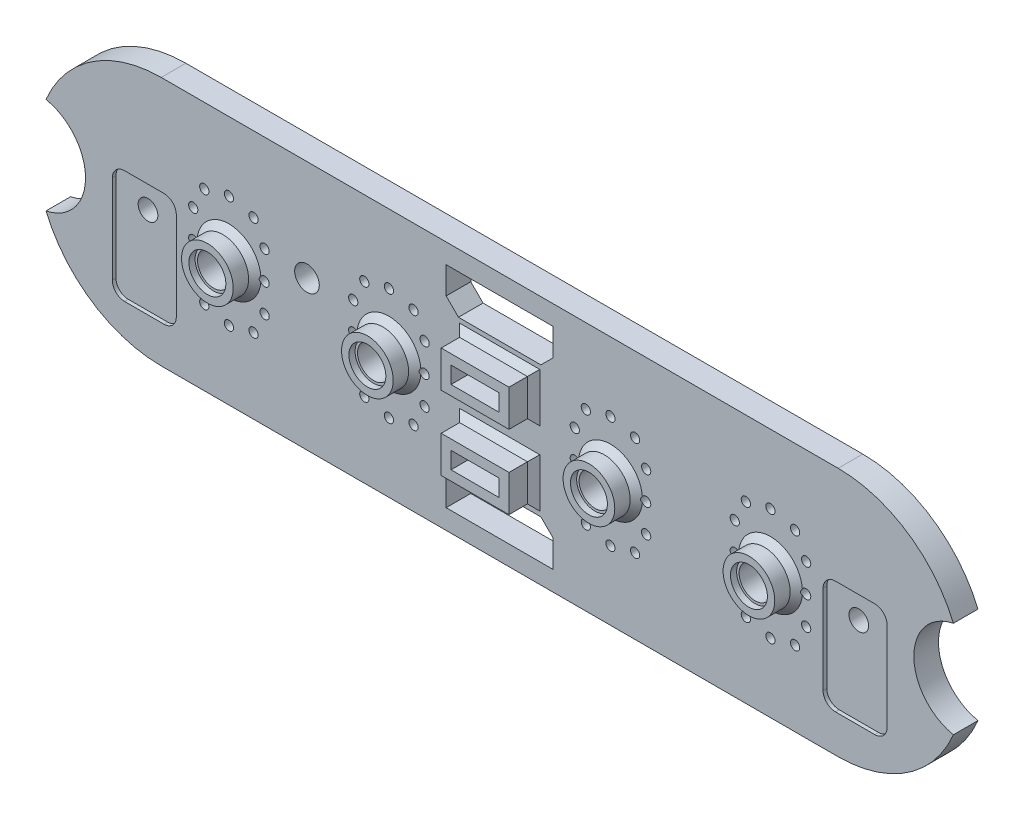
SolidWorks part; units mm, degrees
ref_plane "Plan de face" through (0, 0, 0) normal (0, 0, 1) x (1, 0, 0)
ref_plane "Plan de dessus" through (0, 0, 0) normal (0, 1, 0) x (1, 0, 0)
ref_plane "Plan de droite" through (0, 0, 0) normal (1, 0, 0) x (0, 0, -1)
sketch "Esquisse1" plane through (0, 0, 0) normal (0, 0, 1) x (1, 0, 0)
  line L0 (-55, 0) -> (55, 0) construction
  line L1 (-55, 22.5) -> (55, 22.5) construction
  line L2 (-55, -22.5) -> (55, -22.5) construction
  line L3 (-55, 20.3) -> (55, 20.3)
  line L4 (-55, -20.3) -> (55, -20.3)
  arc A0 (-55, 22.5) -> (-55, -22.5) centre (-55, 0) ccw construction
  arc A1 (55, -22.5) -> (55, 22.5) centre (55, 0) ccw construction
  arc A2 (55, -20.3) -> (55, 20.3) centre (55, 0) ccw
  arc A3 (-55, 20.3) -> (-55, -20.3) centre (-55, 0) ccw
  point P2 (0, 0)
  dimension "D1" = 110
  dimension "D2" = 45
  dimension "D3" = 2.2
extrude "Boss.-Extru.1" add sketch "Esquisse1" along normal blind 4
sketch "Esquisse5" plane through (0, 0, 4) normal (0, 0, 1) x (1, 0, 0)
  line L0 (0, -55) -> (0, 55) construction
  arc A0 (-73.7236, 7.8432) -> (-73.7236, -7.8432) centre (-75.3, 0) cw
  arc A1 (-55, 20.3) -> (-55, -20.3) centre (-55, 0) ccw construction
  arc A2 (-73.7236, 7.8432) -> (-73.7236, -7.8432) centre (-55, 0) ccw
  arc A3 (73.7236, 7.8432) -> (73.7236, -7.8432) centre (75.3, 0) ccw
  arc A4 (73.7236, 7.8432) -> (73.7236, -7.8432) centre (55, 0) cw
  dimension "D1" = 8
extrude "Enlèv. mat.-Extru.2" cut sketch "Esquisse5" against normal through all
sketch "Esquisse6" plane through (0, 0, 4) normal (0, 0, 1) x (1, 0, 0)
  line L1 (-57.75, 0) -> (57.75, 0) construction
  circle A0 centre (-57.75, 0) radius 1.6
  circle A1 centre (57.75, 0) radius 1.6
  point P6 (0, 0)
  dimension "D1" = 3.2
  dimension "D2" = 115.5
extrude "Enlèv. mat.-Extru.3" cut sketch "Esquisse6" against normal through all
sketch "Esquisse7" plane through (0, 0, 4) normal (0, 0, 1) x (1, 0, 0)
  line L1 (-62.75, 4) -> (-52.75, 4) construction
  line L2 (-62.75, 4) -> (-62.75, -14) construction
  line L3 (-62.75, -14) -> (-52.75, -14) construction
  line L4 (-52.75, 4) -> (-52.75, -14) construction
  line L5 (-60.95, 4.2) -> (-54.55, 4.2)
  line L6 (-52.55, 2.2) -> (-52.55, -12.2)
  line L7 (-60.95, -14.2) -> (-54.55, -14.2)
  line L8 (-62.95, 2.2) -> (-62.95, -12.2)
  line L9 (-62.95, 4.2) -> (-62.95, -14.2) construction
  line L10 (-62.95, -14.2) -> (-52.55, -14.2) construction
  line L11 (-52.55, 4.2) -> (-52.55, -14.2) construction
  line L12 (-62.95, 4.2) -> (-52.55, 4.2) construction
  line L13 (0, -55) -> (0, 55) construction
  line L14 (60.95, 4.2) -> (54.55, 4.2)
  line L15 (52.55, 2.2) -> (52.55, -12.2)
  line L16 (60.95, -14.2) -> (54.55, -14.2)
  line L17 (62.95, 2.2) -> (62.95, -12.2)
  arc A1 (-62.95, -12.2) -> (-60.95, -14.2) centre (-60.95, -12.2) ccw
  arc A2 (-52.55, -12.2) -> (-54.55, -14.2) centre (-54.55, -12.2) cw
  arc A3 (-54.55, 4.2) -> (-52.55, 2.2) centre (-54.55, 2.2) cw
  arc A4 (-60.95, 4.2) -> (-62.95, 2.2) centre (-60.95, 2.2) ccw
  arc A5 (60.95, 4.2) -> (62.95, 2.2) centre (60.95, 2.2) cw
  arc A6 (54.55, 4.2) -> (52.55, 2.2) centre (54.55, 2.2) ccw
  arc A7 (52.55, -12.2) -> (54.55, -14.2) centre (54.55, -12.2) ccw
  arc A8 (62.95, -12.2) -> (60.95, -14.2) centre (60.95, -12.2) cw
  circle A9 centre (-57.75, 0) radius 1.6 construction
  dimension "D5" = 2
  dimension "D1" = 10
  dimension "D2" = 18
  dimension "D3" = 4
  dimension "D4" = 0.2
  dimension "D6" = 5
extrude "Enlèv. mat.-Extru.4" cut sketch "Esquisse7" against normal blind 0.6
sketch "Esquisse2" plane through (0, 0, 4) normal (0, 0, 1) x (1, 0, 0)
  line L0 (-18, 0) -> (-12.2, 0) construction
  line L1 (-18, 0) -> (-18, 9.1) construction
  line L2 (0, -55) -> (0, 55) construction
  line L3 (0, -6) -> (0, 6) construction
  line L4 (-18, 0) -> (-13.9991, 8.0953) construction
  line L5 (-13.9991, 8.0953) -> (-18, 0) construction
  line L6 (-18, 0) -> (-12.2007, 4.5965) construction
  line L7 (-3.91, 7.37) -> (3.91, 7.37)
  line L8 (-12.2007, -4.5965) -> (-18, 0) construction
  line L9 (-18, 0) -> (-13.9991, -8.0953) construction
  line L10 (-13.9991, -8.0953) -> (-18, 0) construction
  line L11 (-3.91, 7.37) -> (-3.91, 4.63)
  line L12 (-3.91, 4.63) -> (3.91, 4.63)
  line L13 (-18, -9.1) -> (-18, 0) construction
  line L14 (3.91, 7.37) -> (3.91, 4.63)
  line L15 (-3.91, 7.37) -> (3.91, 4.63) construction
  line L16 (-22.0009, -8.0953) -> (-18, 0) construction
  line L17 (-18, 0) -> (-23.7993, -4.5965) construction
  line L18 (-3.91, 4.63) -> (3.91, 7.37) construction
  line L19 (-23.8, 0) -> (-18, 0) construction
  line L20 (-18, 0) -> (-23.7993, 4.5965) construction
  line L21 (-3.91, -4.63) -> (3.91, -4.63)
  line L22 (-22.0009, 8.0953) -> (-18, 0) construction
  line L23 (-3.91, -4.63) -> (-3.91, -7.37)
  line L24 (-3.91, -7.37) -> (3.91, -7.37)
  line L25 (3.91, -4.63) -> (3.91, -7.37)
  line L26 (-3.91, -4.63) -> (3.91, -7.37) construction
  line L27 (-3.91, -7.37) -> (3.91, -4.63) construction
  circle A0 centre (-18, 9.1) radius 0.75
  circle A1 centre (-13.9991, 8.0953) radius 0.75
  circle A2 centre (-12.2007, 4.5965) radius 0.75
  circle A3 centre (-12.2, 0) radius 0.75
  circle A4 centre (-12.2007, -4.5965) radius 0.75
  circle A5 centre (-13.9991, -8.0953) radius 0.75
  circle A6 centre (-18, -9.1) radius 0.75
  circle A7 centre (-22.0009, -8.0953) radius 0.75
  circle A8 centre (-23.7993, -4.5965) radius 0.75
  circle A9 centre (-23.8, 0) radius 0.75
  circle A10 centre (-23.7993, 4.5965) radius 0.75
  circle A11 centre (-22.0009, 8.0953) radius 0.75
  circle A12 centre (-18, 0) radius 2.6
  circle A13 centre (-48.0009, 8.0953) radius 0.75
  circle A14 centre (-49.7993, 4.5965) radius 0.75
  circle A15 centre (-49.8, 0) radius 0.75
  circle A16 centre (-49.7993, -4.5965) radius 0.75
  circle A17 centre (-44, 0) radius 2.6
  circle A18 centre (-48.0009, -8.0953) radius 0.75
  circle A19 centre (-44, -9.1) radius 0.75
  circle A20 centre (-39.9991, -8.0953) radius 0.75
  circle A21 centre (-38.2007, -4.5965) radius 0.75
  circle A22 centre (-38.2, 0) radius 0.75
  circle A23 centre (-38.2007, 4.5965) radius 0.75
  circle A24 centre (-39.9991, 8.0953) radius 0.75
  circle A25 centre (-44, 9.1) radius 0.75
  circle A26 centre (44, 9.1) radius 0.75
  circle A27 centre (39.9991, 8.0953) radius 0.75
  circle A28 centre (38.2007, 4.5965) radius 0.75
  circle A29 centre (38.2, 0) radius 0.75
  circle A30 centre (38.2007, -4.5965) radius 0.75
  circle A31 centre (39.9991, -8.0953) radius 0.75
  circle A32 centre (44, -9.1) radius 0.75
  circle A33 centre (48.0009, -8.0953) radius 0.75
  circle A34 centre (44, 0) radius 2.6
  circle A35 centre (49.7993, -4.5965) radius 0.75
  circle A36 centre (49.8, 0) radius 0.75
  circle A37 centre (49.7993, 4.5965) radius 0.75
  circle A38 centre (48.0009, 8.0953) radius 0.75
  circle A39 centre (18, 9.1) radius 0.75
  circle A40 centre (13.9991, 8.0953) radius 0.75
  circle A41 centre (12.2007, 4.5965) radius 0.75
  circle A42 centre (12.2, 0) radius 0.75
  circle A43 centre (12.2007, -4.5965) radius 0.75
  circle A44 centre (13.9991, -8.0953) radius 0.75
  circle A45 centre (18, -9.1) radius 0.75
  circle A46 centre (22.0009, -8.0953) radius 0.75
  circle A47 centre (18, 0) radius 2.6
  circle A48 centre (23.7993, -4.5965) radius 0.75
  circle A49 centre (23.8, 0) radius 0.75
  circle A50 centre (23.7993, 4.5965) radius 0.75
  circle A51 centre (22.0009, 8.0953) radius 0.75
  point P2 (0, 6)
  point P112 (0, -6)
  point P120 (0, 0)
  dimension "D10" = 1.5
  dimension "D11" = 5.2
  dimension "D1" = 5.8
  dimension "D2" = 7.4
  dimension "D3" = 9.03
  dimension "D4" = 18
  dimension "D5" = 9.1
  dimension "D6" = 38.4
  dimension "D7" = 63.7
  dimension "D8" = 38.4
  dimension "D9" = 63.7
  dimension "D13" = 12
  dimension "D14" = 2.74
  dimension "D15" = 7.82
  dimension "D12" = 2
extrude "Enlèv. mat.-Extru.1" cut sketch "Esquisse2" against normal through all
sketch "Esquisse3" plane through (0, 0, 4) normal (0, 0, 1) x (1, 0, 0)
  circle A1 centre (-18, 0) radius 2.6 construction
  circle A2 centre (-18, 0) radius 2.6
  circle A4 centre (44, 0) radius 2.6 construction
  circle A5 centre (18, 0) radius 2.6 construction
  circle A6 centre (-44, 0) radius 2.6 construction
  circle A7 centre (44, 0) radius 2.6
  circle A8 centre (18, 0) radius 2.6
  circle A9 centre (-44, 0) radius 2.6
  circle A10 centre (-44, 0) radius 4.2
  circle A11 centre (-18, 0) radius 4.2
  circle A12 centre (18, 0) radius 4.2
  circle A13 centre (44, 0) radius 4.2
  dimension "D1" = 1.6
extrude "Boss.-Extru.2" add sketch "Esquisse3" along normal blind 3.5
sketch "Esquisse9" plane through (0, 0, 7.5) normal (0, 0, 1) x (1, 0, 0)
  circle A0 centre (-44, 0) radius 3
  circle A1 centre (-18, 0) radius 3
  circle A2 centre (18, 0) radius 3
  circle A3 centre (44, 0) radius 3
  dimension "D1" = 6
extrude "Enlèv. mat.-Extru.6" cut sketch "Esquisse9" against normal blind 1
sketch "Esquisse4" plane through (0, 0, 4) normal (0, 0, 1) x (1, 0, 0)
  line L2 (5.51, -8.97) -> (5.51, -3.03)
  line L3 (5.51, -3.03) -> (-5.51, -3.03)
  line L4 (-5.51, -3.03) -> (-5.51, -8.97)
  line L5 (-5.51, -8.97) -> (5.51, -8.97)
  line L6 (3.91, -7.37) -> (3.91, -4.63)
  line L7 (-3.91, -7.37) -> (3.91, -7.37)
  line L8 (-3.91, -4.63) -> (-3.91, -7.37)
  line L9 (3.91, -4.63) -> (-3.91, -4.63)
  line L10 (3.91, -7.37) -> (3.91, -4.63)
  line L11 (-3.91, -7.37) -> (3.91, -7.37)
  line L12 (-3.91, -4.63) -> (-3.91, -7.37)
  line L13 (3.91, -4.63) -> (-3.91, -4.63)
  line L14 (3.91, 4.63) -> (3.91, 7.37)
  line L15 (-3.91, 4.63) -> (3.91, 4.63)
  line L16 (-3.91, 7.37) -> (-3.91, 4.63)
  line L17 (3.91, 7.37) -> (-3.91, 7.37)
  line L18 (3.91, 4.63) -> (3.91, 7.37)
  line L19 (-3.91, 4.63) -> (3.91, 4.63)
  line L20 (-3.91, 7.37) -> (-3.91, 4.63)
  line L21 (3.91, 7.37) -> (-3.91, 7.37)
  line L22 (5.51, 3.03) -> (5.51, 8.97)
  line L23 (5.51, 8.97) -> (-5.51, 8.97)
  line L24 (-5.51, 8.97) -> (-5.51, 3.03)
  line L25 (-5.51, 3.03) -> (5.51, 3.03)
  dimension "D1" = 0
  dimension "D2" = 0
  dimension "D3" = 1.6
extrude "Boss.-Extru.3" add sketch "Esquisse4" along normal offset from surface (4 mm away) 8 up to face at (-47.2509, 8.0953, 0)
chamfer "Chanfrein1" distance 1 angle 45 12 edges at (48.2, 0, 4) (22.2, 0, 4) (-13.8, 0, 4) (-39.8, 0, 4) (0, -3.03, 4) (5.51, -6, 4) (0, -8.97, 4) (-5.51, -6, 4) (0, 3.03, 4) (-5.51, 6, 4) (5.51, 6, 4) (0, 8.97, 4)
fillet "Congé1" radius 2 4 edges at (-41.4, 0, 0) (-15.4, 0, 0) (15.4, 0, 0) (41.4, 0, 0)
sketch "Esquisse8" plane through (0, 0, 4) normal (0, 0, 1) x (1, 0, 0)
  line L0 (55, 20.3) -> (-55, 20.3) construction
  line L1 (-8.7, 17.1) -> (8.7, 17.1)
  line L2 (-8.7, 17.1) -> (-8.7, 12.7)
  line L3 (-6.7, 10.7) -> (6.7, 10.7)
  line L4 (8.7, 17.1) -> (8.7, 12.7)
  line L5 (0, 20.3) -> (0, 17.1) construction
  line L6 (-8.7, 12.7) -> (-6.7, 10.7)
  line L7 (6.7, 10.7) -> (8.7, 12.7)
  line L8 (4.4, 0) -> (-4.4, 0) construction
  line L9 (-8.7, -17.1) -> (-8.7, -12.7)
  line L10 (-8.7, -12.7) -> (-6.7, -10.7)
  line L11 (-6.7, -10.7) -> (6.7, -10.7)
  line L12 (6.7, -10.7) -> (8.7, -12.7)
  line L13 (8.7, -17.1) -> (8.7, -12.7)
  line L14 (-8.7, -17.1) -> (8.7, -17.1)
  circle A0 centre (-31.3151, 3.9002) radius 2
  point P1 (8.7, 10.7)
  point P2 (-8.7, 10.7)
  point P22 (-31.3151, 3.9002)
  dimension "D4" = 4
  dimension "D1" = 17.4
  dimension "D2" = 6.4
  dimension "D3" = 3.2
extrude "Enlèv. mat.-Extru.5" cut sketch "Esquisse8" against normal through all
